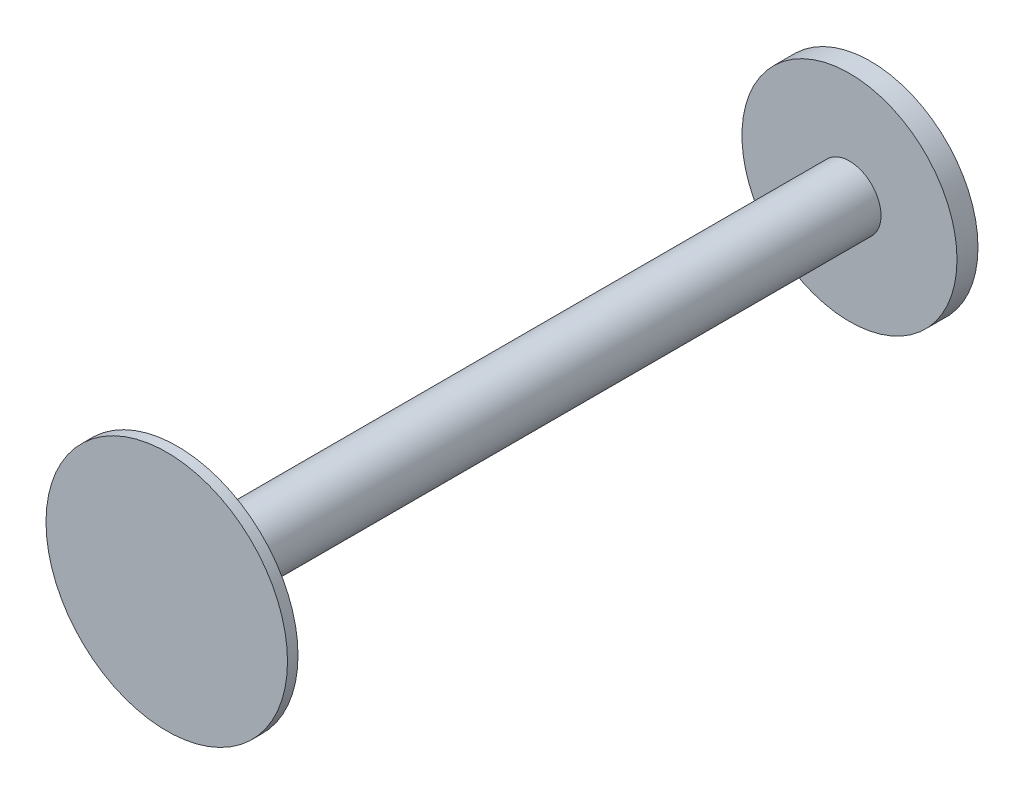
SolidWorks part; units mm, degrees
ref_plane "Front Plane" through (0, 0, 0) normal (0, 0, 1) x (1, 0, 0)
ref_plane "Top Plane" through (0, 0, 0) normal (0, 1, 0) x (1, 0, 0)
ref_plane "Right Plane" through (0, 0, 0) normal (1, 0, 0) x (0, 0, -1)
sketch "Sketch1" plane through (0, 0, 0) normal (0, 0, 1) x (1, 0, 0)
  circle A0 centre (0, 0) radius 32.5
  dimension "D1" = 65
extrude "Boss-Extrude1" add sketch "Sketch1" along normal blind 6.35
sketch "Sketch2" plane through (0, 0, 6.35) normal (0, 0, 1) x (1, 0, 0)
  circle A0 centre (0, 0) radius 9.525
  dimension "D1" = 19.05
extrude "Boss-Extrude2" add sketch "Sketch2" along normal blind 203.2
sketch "Sketch3" plane through (0, 0, 209.55) normal (0, 0, 1) x (1, 0, 0)
  circle A0 centre (0, 0) radius 36.5
  dimension "D1" = 73
extrude "Boss-Extrude3" add sketch "Sketch3" along normal blind 3.175
